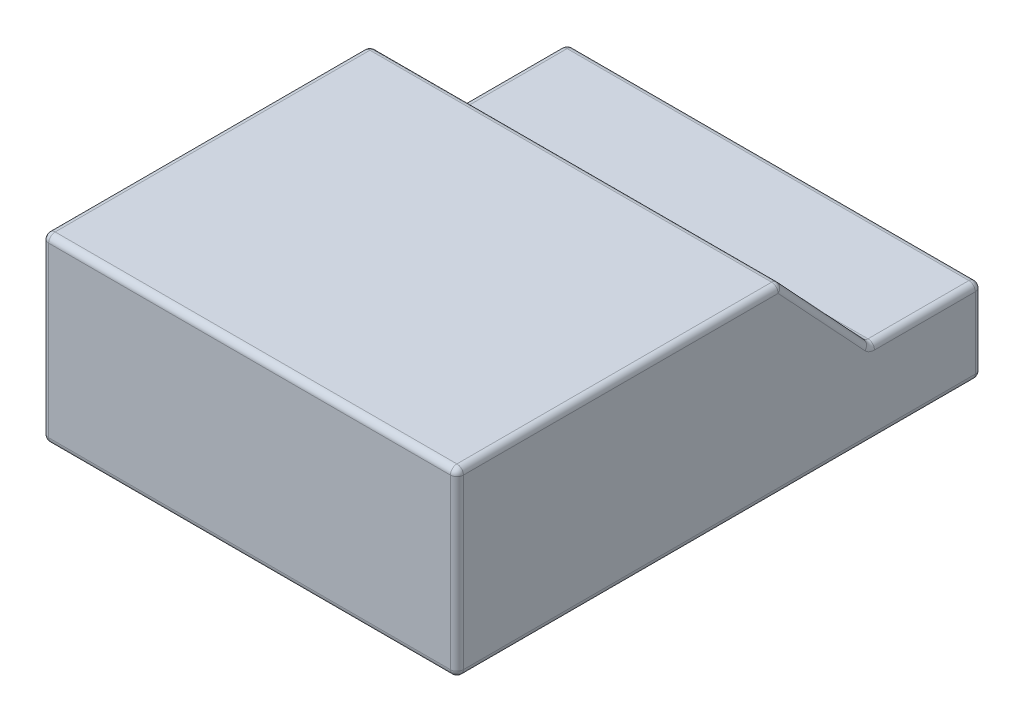
SolidWorks part; units mm, degrees
ref_plane "Front Plane" through (0, 0, 0) normal (0, 0, 1) x (1, 0, 0)
ref_plane "Top Plane" through (0, 0, 0) normal (0, 1, 0) x (1, 0, 0)
ref_plane "Right Plane" through (0, 0, 0) normal (1, 0, 0) x (0, 0, -1)
sketch "Sketch1" plane through (0, 0, 0) normal (0, 0, 1) x (1, 0, 0)
  line L0 (0, 0) -> (0, 11)
  line L1 (0, 11) -> (60, 11)
  line L2 (60, 11) -> (60, 0)
  line L3 (60, 0) -> (62, 0)
  line L4 (62, 0) -> (62, 13)
  line L5 (62, 13) -> (-2, 13)
  line L6 (-2, 13) -> (-2, 0)
  line L7 (-2, 0) -> (0, 0)
  point P10 (-1, 0)
  dimension "D1" = 2
  dimension "D2" = 2
  dimension "D3" = 64
  dimension "D4" = 2
  dimension "D5" = 13
extrude "Boss-Extrude1" add sketch "Sketch1" along normal blind 17
sketch "Sketch2" plane through (0, 0, 0) normal (0, 0, -1) x (-1, 0, 0)
  line L1 (-60, 11) -> (0, 11)
  line L2 (-60, 11) -> (-60, 0)
  line L3 (-60, 0) -> (0, 0)
  line L4 (0, 11) -> (0, 0)
extrude "Boss-Extrude2" add sketch "Sketch2" against normal blind 1
sketch "Sketch4" plane through (-2, 0, 0) normal (-1, 0, 0) x (0, 0, 1)
  line L0 (17, 13) -> (31, 28)
  line L1 (31, 28) -> (81, 28)
  line L2 (81, 28) -> (81, 0)
  line L3 (81, 0) -> (17, 0)
  line L4 (17, 0) -> (17, 13)
  dimension "D1" = 64
  dimension "D2" = 50
  dimension "D3" = 15
extrude "Boss-Extrude3" add sketch "Sketch4" against normal blind 64
ref_plane "Plane1" through (0, 0, 0) normal (-1, 0, 0) x (0, 0, 1)
sketch "Sketch6" plane through (0, 0, 0) normal (-1, 0, 0) x (0, 0, 1)
  line L0 (17, 13) -> (17, 0) construction
  line L1 (19, 0) -> (19, 12.2117)
  line L2 (81, 0) -> (0, 0) construction
  line L3 (19, 12.2117) -> (31.8691, 26)
  line L4 (31.8691, 26) -> (79, 26)
  line L5 (79, 26) -> (79, 0)
  line L6 (79, 0) -> (19, 0)
  line L7 (31, 28) -> (17, 13) construction
  line L8 (81, 28) -> (31, 28) construction
  line L9 (81, 0) -> (81, 28) construction
  dimension "D1" = 2
  dimension "D2" = 2
  dimension "D3" = 2
  dimension "D4" = 2
extrude "Cut-Extrude1" cut sketch "Sketch6" against normal blind 60 contours L6 L1 L3 L4 L5
fillet "Fillet1" radius 1 19 edges at (62, 0, 40.5) (62, 13, 8.5) (62, 6.5, 0) (30, 13, 0) (30, 0, 0) (62, 14, 81) (30, 0, 81) (62, 28, 56) (30, 28, 81) (-2, 13, 8.5) (-2, 28, 56) (-2, 14, 81) (-2, 0, 40.5) (-2, 6.5, 0) (30, 13, 17) (62, 20.5, 24) (30, 28, 31) (-2, 20.5, 24) (30, 11, 1)
